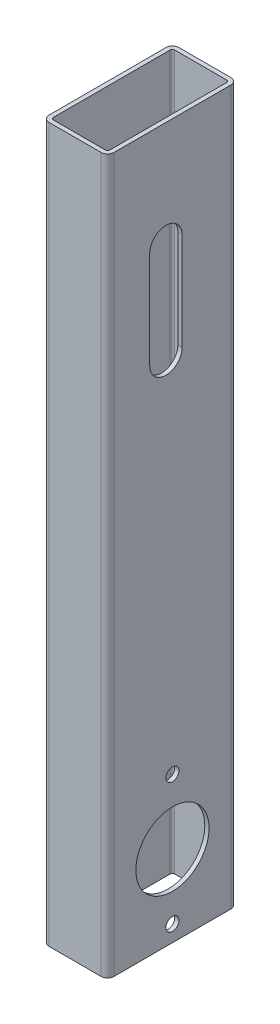
SolidWorks part; units mm, degrees
material "6061-T6 (SS)"
ref_plane "Front Plane" through (0, 0, 0) normal (0, 0, 1) x (1, 0, 0)
ref_plane "Top Plane" through (0, 0, 0) normal (0, 1, 0) x (1, 0, 0)
ref_plane "Right Plane" through (0, 0, 0) normal (1, 0, 0) x (0, 0, -1)
sketch "Sketch1" plane through (0, 0, 0) normal (0, 1, 0) x (1, 0, 0)
  line L1 (10.16, -25.4) -> (-10.16, -25.4)
  line L2 (12.7, -22.86) -> (12.7, 22.86)
  line L3 (10.16, 25.4) -> (-10.16, 25.4)
  line L4 (-12.7, -22.86) -> (-12.7, 22.86)
  line L5 (12.7, -25.4) -> (-12.7, 25.4) construction
  line L6 (12.7, 25.4) -> (-12.7, -25.4) construction
  arc A0 (-10.16, -25.4) -> (-12.7, -22.86) centre (-10.16, -22.86) cw
  arc A1 (10.16, -25.4) -> (12.7, -22.86) centre (10.16, -22.86) ccw
  arc A2 (12.7, 22.86) -> (10.16, 25.4) centre (10.16, 22.86) ccw
  arc A3 (-10.16, 25.4) -> (-12.7, 22.86) centre (-10.16, 22.86) ccw
  point P0 (0, 0)
  dimension "D3" = 2.54
  dimension "D1" = 25.4
  dimension "D2" = 50.8
extrude "Extrude-Thin1" add sketch "Sketch1" along normal blind 203.2 and the other way blind 76.2 thin thin type one direction reverse wall 1.651
sketch "Sketch2" plane through (-12.7, 0, 0) normal (-1, 0, 0) x (0, 0, 1)
  line L0 (2.54, 161.9426) -> (2.54, 12.7) construction
  line L4 (9.2075, 161.9426) -> (9.2075, 12.7)
  line L5 (-4.1275, 161.9426) -> (-4.1275, 12.7)
  line L6 (2.54, 25.4) -> (2.54, 149.2426) construction
  arc A2 (9.2075, 161.9426) -> (-4.1275, 161.9426) centre (2.54, 161.9426) ccw
  arc A3 (-4.1275, 12.7) -> (9.2075, 12.7) centre (2.54, 12.7) ccw
  point P2 (-118.6195, 53.8305)
  point P3 (2.54, 87.3213)
  dimension "D5" = 13.335
  dimension "D2" = 12.7
  dimension "D1" = 12.7
extrude "Cut-Extrude1" cut sketch "Sketch2" against normal up to next
sketch "Sketch5" plane through (12.7, 0, 0) normal (1, 0, 0) x (0, 0, -1)
  line L0 (-2.54, 161.9426) -> (-2.54, 123.8426) construction
  line L1 (3.81, 161.9426) -> (3.81, 123.8426)
  line L2 (-8.89, 161.9426) -> (-8.89, 123.8426)
  arc A0 (3.81, 161.9426) -> (-8.89, 161.9426) centre (-2.54, 161.9426) ccw
  arc A1 (-8.89, 123.8426) -> (3.81, 123.8426) centre (-2.54, 123.8426) ccw
  arc A2 (4.1275, 161.9426) -> (-9.2075, 161.9426) centre (-2.54, 161.9426) ccw construction
  point P2 (-2.54, 142.8926)
  dimension "D1" = 6.35
  dimension "D2" = 38.1
extrude "Cut-Extrude4" cut sketch "Sketch5" against normal up to next
sketch "Sketch4" plane through (-12.7, 0, 0) normal (1, 0, 0) x (0, 0, -1)
  circle A12 centre (11.049, 4.7713) radius 2.5527
  circle A13 centre (-16.129, 4.7713) radius 2.5527
  circle A14 centre (-16.129, 87.3213) radius 2.5527
  circle A15 centre (11.049, 87.3213) radius 2.5527
  circle A16 centre (-16.129, 169.8713) radius 2.5527
  circle A17 centre (11.049, 169.8713) radius 2.5527
  dimension "D1" = 5.1054
extrude "Cut-Extrude3" cut sketch "Sketch4" along normal up to surface (1.651 mm away) up to face at (-11.049, 87.3213, 2.54)
sketch "Sketch6" plane through (12.7, 0, 0) normal (1, 0, 0) x (0, 0, -1)
  line L0 (25.4, -76.2) -> (25.4, 203.2) construction
  circle A0 centre (0, -44.45) radius 14.3256
  dimension "D1" = 28.6512
  dimension "D2" = 25.4
  dimension "D3" = 44.45
extrude "Cut-Extrude5" cut sketch "Sketch6" against normal through all
hole_wizard "#10 Clearance Hole1" positions "Sketch8" profile "Sketch9" hole size "#10" standard "ANSI Inch" end condition through all
sketch "Sketch8" plane through (12.7, 0, 0) normal (1, 0, 0) x (0, 0, -1)
  circle A0 centre (0, -44.45) radius 25.4 construction
  point P0 (0, -19.05)
  point P11 (0, -69.85)
  dimension "D1" = 50.8
sketch "Sketch9" plane through (12.7, -19.05, 0) normal (0, 1, 0) x (0, 0, -1)
  line L0 (0, 0) -> (0, 25.4)
  line L1 (0, 25.4) -> (2.5527, 25.4)
  line L2 (2.5527, 25.4) -> (2.5527, 0)
  line L5 (2.5527, 0) -> (0, 0)
  line L11 (0, -6.35) -> (0, 107.95) construction
  dimension "Thru Hole Dia." = 5.1054
  dimension "Thru Hole Depth" = 25.4
